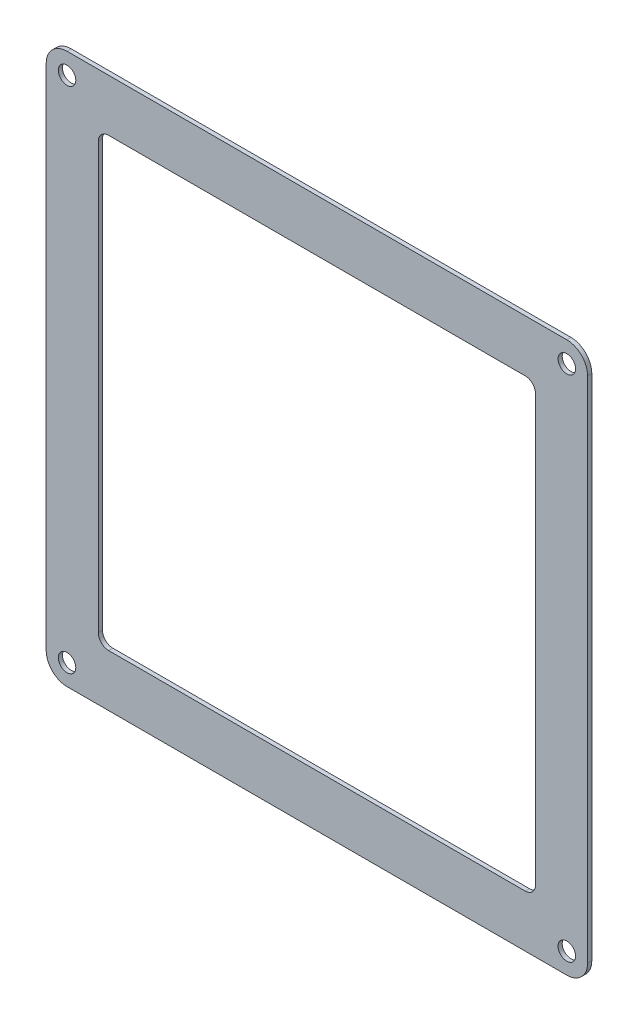
SolidWorks part; units mm, degrees
material "天然橡胶"
ref_plane "前视基准面" through (0, 0, 0) normal (0, 0, 1) x (1, 0, 0)
ref_plane "上视基准面" through (0, 0, 0) normal (0, 1, 0) x (1, 0, 0)
ref_plane "右视基准面" through (0, 0, 0) normal (1, 0, 0) x (0, 0, -1)
sketch "草图1" plane through (0, 0, 0) normal (0, 0, 1) x (1, 0, 0)
  line L1 (-105, -107.125) -> (105, -107.125)
  line L2 (-105, -107.125) -> (-105, 107.125)
  line L3 (-105, 107.125) -> (105, 107.125)
  line L4 (105, -107.125) -> (105, 107.125)
  line L5 (-105, -107.125) -> (105, 107.125) construction
  line L6 (-105, 107.125) -> (105, -107.125) construction
  line L7 (-130, -132.125) -> (130, -132.125)
  line L8 (-130, -132.125) -> (-130, 132.125)
  line L9 (-130, 132.125) -> (130, 132.125)
  line L10 (130, -132.125) -> (130, 132.125)
  line L11 (-130, -132.125) -> (130, 132.125) construction
  line L12 (-130, 132.125) -> (130, -132.125) construction
  point P0 (0, 0)
  point P6 (0, 0)
  dimension "D1" = 210
  dimension "D2" = 214.25
  dimension "D3" = 25
  dimension "D4" = 25
extrude "凸台-拉伸1" add sketch "草图1" along normal blind 2
fillet "圆角1" radius 10 4 edges at (130, 132.125, 1) (130, -132.125, 1) (-130, -132.125, 1) (-130, 132.125, 1)
fillet "圆角2" radius 5 4 edges at (-105, 107.125, 1) (-105, -107.125, 1) (105, -107.125, 1) (105, 107.125, 1)
hole_wizard "Ø8.4 (8.4) 直径孔1" positions "草图2" profile "草图3" hole size "Ø8.4" standard "GB" end condition through all
sketch "草图2" plane through (0, 0, 2) normal (0, 0, 1) x (1, 0, 0)
  point P0 (120, -122.125)
  point P3 (-120, 122.125)
  point P6 (-120, -122.125)
  point P9 (120, 122.125)
sketch "草图3" plane through (120, -122.125, 2) normal (1, 0, 0) x (0, -1, 0)
  line L0 (0, 0) -> (0, 2)
  line L1 (0, 2) -> (4.2, 2)
  line L2 (4.2, 2) -> (4.2, 0)
  line L5 (4.2, 0) -> (0, 0)
  line L11 (0, -6.35) -> (0, 107.95) construction
  dimension "通孔孔直径" = 8.4
  dimension "通孔孔深度" = 2
